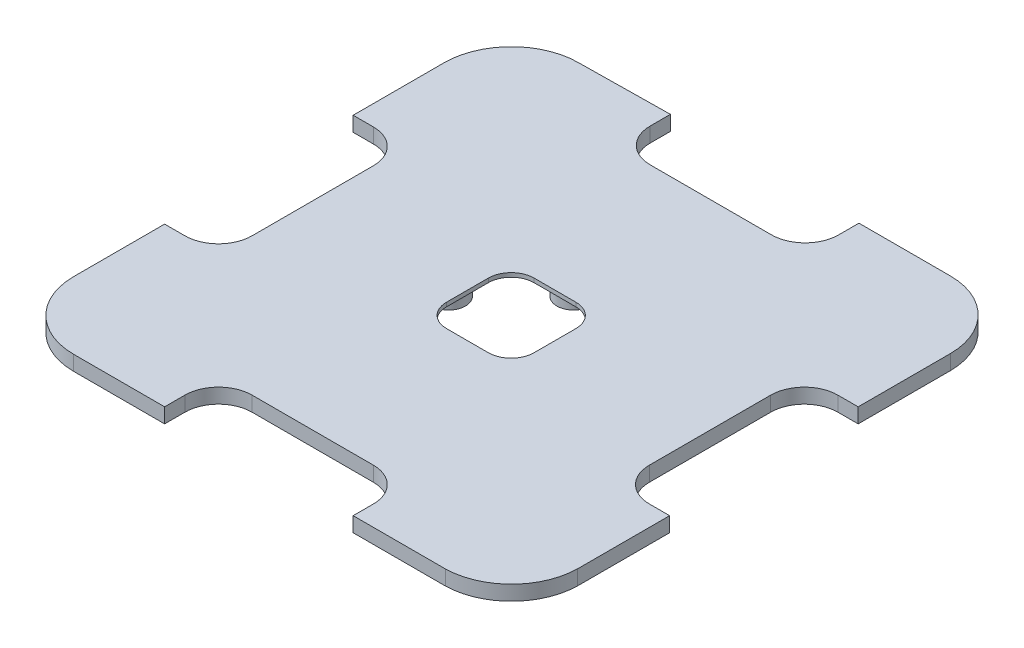
SolidWorks part; units mm, degrees
ref_plane "Front Plane" through (0, 0, 0) normal (0, 0, 1) x (1, 0, 0)
ref_plane "Top Plane" through (0, 0, 0) normal (0, 1, 0) x (1, 0, 0)
ref_plane "Right Plane" through (0, 0, 0) normal (1, 0, 0) x (0, 0, -1)
sketch "Sketch6" plane through (0, 0, 0) normal (0, 1, 0) x (1, 0, 0)
  line L0 (-27.9543, -74.9894) -> (-27.9543, -68.9894)
  line L4 (-54.9544, -74.9894) -> (-27.9543, -74.9894)
  line L8 (28.0457, -74.9894) -> (28.0457, -68.9894)
  line L9 (18.0457, -58.9894) -> (-17.9543, -58.9894)
  line L10 (28.0457, -74.9894) -> (55.5119, -74.9894)
  line L11 (27.922, 75.3686) -> (27.9223, 69.3686)
  line L12 (-18.0772, 59.3662) -> (17.9228, 59.3681)
  line L13 (-28.078, 75.3657) -> (-28.0777, 69.3657)
  line L14 (-28.078, 75.3657) -> (-54.9215, 75.0001)
  line L15 (27.922, 75.3686) -> (55.0446, 75.3701)
  line L16 (-74.9543, 28.0106) -> (-68.9543, 28.0106)
  line L17 (-58.9543, -17.9894) -> (-58.9543, 18.0106)
  line L18 (-74.9543, -27.9894) -> (-68.9543, -27.9894)
  line L22 (75.0457, -27.9894) -> (69.0457, -27.9894)
  line L23 (59.0457, 18.0106) -> (59.0457, -17.9894)
  line L24 (75.0457, 28.0106) -> (69.0457, 28.0106)
  line L25 (75.0457, 28.0106) -> (75.0457, 55.37)
  line L26 (75.0457, -27.9894) -> (75.0457, -55.3762)
  line L27 (-74.9543, 55.0001) -> (-74.9543, 28.0106)
  line L28 (-74.9543, -27.9894) -> (-74.9543, -54.9895)
  line L29 (-73.4543, 55.0001) -> (-73.4543, 29.5106)
  line L30 (-73.4543, 29.5106) -> (-68.9543, 29.5106)
  line L31 (-57.4543, -17.9894) -> (-57.4543, 18.0106)
  line L32 (-73.4543, -29.4894) -> (-68.9543, -29.4894)
  line L33 (-73.4543, -29.4894) -> (-73.4543, -54.9895)
  line L34 (-54.9544, -73.4894) -> (-36.0728, -73.4894)
  line L35 (-29.4543, -73.4894) -> (-29.4543, -68.9894)
  line L36 (18.0457, -57.4894) -> (-17.9543, -57.4894)
  line L37 (29.5457, -73.4894) -> (29.5457, -68.9894)
  line L38 (29.5457, -73.4894) -> (55.4924, -73.4894)
  line L39 (73.5457, -29.4894) -> (73.5457, -55.3598)
  line L40 (73.5457, -29.4894) -> (69.0457, -29.4894)
  line L41 (57.5457, 18.0106) -> (57.5457, -17.9894)
  line L42 (73.5457, 29.5106) -> (69.0457, 29.5106)
  line L43 (73.5457, 29.5106) -> (73.5457, 55.37)
  line L44 (29.4221, 73.8687) -> (55.0447, 73.8701)
  line L45 (29.4221, 73.8687) -> (29.4223, 69.3687)
  line L46 (-18.0771, 57.8662) -> (17.9229, 57.8681)
  line L47 (-29.5779, 73.8451) -> (-29.5777, 69.3656)
  line L48 (-29.5779, 73.8451) -> (-54.9127, 73.5)
  line L49 (-34.4232, -73.4894) -> (-32.1323, -73.4894)
  line L50 (-54.9544, -73.4894) -> (-29.4543, -73.4894) construction
  line L51 (-30.4828, -73.4894) -> (-29.4543, -73.4894)
  line L52 (-27.9543, 75.0106) -> (-27.9543, 69.0106) [skipped]
  line L53 (28.0457, 75.0106) -> (28.0457, 69.0106) [skipped]
  line L54 (-17.9543, 59.0106) -> (18.0457, 59.0106) [skipped]
  circle A0 centre (-63.8144, 56.4001) radius 4.1
  circle A1 centre (-56.2944, 63.8801) radius 4.1
  circle A2 centre (-45.5, 65.0002) radius 4.1
  circle A3 centre (-33.77, 60.5602) radius 4.1
  circle A5 centre (-47.06, 47.0602) radius 4.1
  circle A6 centre (-65, 45.5702) radius 4.1
  circle A7 centre (-22.73, 52.0902) radius 4.1
  circle A8 centre (-10.97, 52.0902) radius 4.1
  circle A9 centre (-13.21, 40.9602) radius 4.1
  circle A10 centre (-5.58, 29.2102) radius 4.1
  circle A11 centre (-39.63, 39.6302) radius 4.1
  circle A12 centre (-32.2, 32.2002) radius 4.1
  circle A13 centre (-24.77, 24.7702) radius 4.1
  circle A14 centre (-60.62, 33.8602) radius 4.1
  circle A15 centre (-52.09, 22.8302) radius 4.1
  circle A17 centre (-52.09, 10.9702) radius 4.1
  circle A18 centre (-41.09, 13.3102) radius 4.1
  circle A19 centre (-29.37, 5.6802) radius 4.1
  circle A21 centre (56.4456, 64.23) radius 4.1
  circle A22 centre (63.9256, 56.71) radius 4.1
  circle A23 centre (65, 45.5002) radius 4.1
  circle A24 centre (45.57, 65.0002) radius 4.1
  circle A25 centre (33.86, 60.6202) radius 4.1
  circle A26 centre (47.06, 47.0602) radius 4.1
  circle A27 centre (39.63, 39.6302) radius 4.1
  circle A28 centre (22.83, 52.0902) radius 4.1
  circle A30 centre (10.97, 52.0902) radius 4.1
  circle A31 centre (13.31, 41.0902) radius 4.1
  circle A32 centre (5.68, 29.3702) radius 4.1
  circle A33 centre (24.77, 24.7702) radius 4.1
  circle A34 centre (32.2, 32.2002) radius 4.1
  circle A35 centre (60.56, 33.7702) radius 4.1
  circle A36 centre (52.09, 22.7302) radius 4.1
  circle A38 centre (52.09, 10.9702) radius 4.1
  circle A39 centre (40.96, 13.2102) radius 4.1
  circle A40 centre (29.21, 5.5802) radius 4.1
  circle A42 centre (63.8611, -56.3467) radius 4.1
  circle A43 centre (56.3411, -63.8267) radius 4.1
  circle A44 centre (45.5, -64.9998) radius 4.1
  circle A45 centre (65, -45.5698) radius 4.1
  circle A46 centre (60.62, -33.8598) radius 4.1
  circle A47 centre (47.06, -47.0598) radius 4.1
  circle A48 centre (39.63, -39.6298) radius 4.1
  circle A49 centre (52.09, -22.8298) radius 4.1
  circle A51 centre (52.09, -10.9698) radius 4.1
  circle A52 centre (41.09, -13.3098) radius 4.1
  circle A53 centre (29.37, -5.6798) radius 4.1
  circle A54 centre (24.77, -24.7698) radius 4.1
  circle A55 centre (32.2, -32.1998) radius 4.1
  circle A56 centre (33.77, -60.5598) radius 4.1
  circle A57 centre (22.73, -52.0898) radius 4.1
  circle A59 centre (10.97, -52.0898) radius 4.1
  circle A60 centre (13.21, -40.9598) radius 4.1
  circle A61 centre (5.58, -29.2098) radius 4.1
  circle A63 centre (-56.3544, -63.8492) radius 4.1
  circle A64 centre (-63.8344, -56.3292) radius 4.1
  circle A65 centre (-65, -45.4998) radius 4.1
  circle A66 centre (-45.57, -64.9998) radius 4.1
  circle A67 centre (-33.86, -60.6198) radius 4.1
  circle A68 centre (-47.06, -47.0598) radius 4.1
  circle A69 centre (-39.63, -39.6298) radius 4.1
  circle A70 centre (-22.83, -52.0898) radius 4.1
  circle A72 centre (-10.97, -52.0898) radius 4.1
  circle A73 centre (-13.21, -41.1198) radius 4.1
  circle A74 centre (-5.68, -29.3698) radius 4.1
  circle A75 centre (-24.77, -24.7698) radius 4.1
  circle A76 centre (-32.2, -32.1998) radius 4.1
  circle A77 centre (-60.56, -33.7698) radius 4.1
  circle A78 centre (-52.09, -22.7298) radius 4.1
  circle A80 centre (-52.09, -10.9698) radius 4.1
  circle A81 centre (-40.96, -13.2098) radius 4.1
  circle A82 centre (-29.21, -5.5798) radius 4.1
  circle A85 centre (0, 52.0902) radius 4.1
  circle A86 centre (0, 41.1202) radius 4.1
  circle A87 centre (0, 18.5802) radius 4.1
  circle A89 centre (52.09, 0.0002) radius 4.1
  circle A90 centre (41.12, 0.0002) radius 4.1
  circle A91 centre (18.58, 0.0002) radius 4.1
  circle A93 centre (0, -51.9998) radius 4.1
  circle A94 centre (0, -41.1198) radius 4.1
  circle A95 centre (0, -18.5798) radius 4.1
  circle A97 centre (-52.09, 0.0002) radius 4.1
  circle A98 centre (-41.12, 0.0002) radius 4.1
  circle A99 centre (-18.58, 0.0002) radius 4.1
  arc A105 (-32.1323, -73.4894) -> (-34.4232, -73.4894) centre (-33.2778, -70.9893) ccw
  circle A106 centre (-54.9544, 55.0001) radius 1.85
  circle A107 centre (55.0456, 55.37) radius 1.85
  circle A108 centre (17, 17.0002) radius 1.85
  circle A109 centre (-17, 17.0002) radius 1.85
  circle A110 centre (-17, -16.9998) radius 1.85
  circle A111 centre (17, -16.9998) radius 1.85
  circle A112 centre (-54.9544, -54.9895) radius 1.85
  circle A113 centre (55.001, -54.9467) radius 1.85
  arc A114 (-55.8403, 58.9008) -> (-58.8318, 55.9826) centre (-54.9544, 55.0001) ccw
  circle A115 centre (-17, 17.0002) radius 4
  circle A116 centre (-17, -16.9998) radius 4
  arc A117 (-55.2138, -58.981) -> (-58.9428, -55.2938) centre (-54.9544, -54.9895) ccw
  circle A118 centre (17, -16.9998) radius 4
  arc A119 (55.8869, -58.8474) -> (58.8786, -55.9289) centre (55.001, -54.9467) ccw
  circle A120 centre (17, 17.0002) radius 4
  arc A121 (55.3065, 59.3615) -> (59.034, 55.6746) centre (55.0456, 55.37) ccw
  arc A122 (-74.9543, 55.0001) -> (-54.9215, 75.0001) centre (-54.9544, 55.0001) cw
  arc A123 (75.0457, 55.37) -> (55.0446, 75.3701) centre (55.0456, 55.37) ccw
  arc A124 (-74.9543, -54.9895) -> (-54.9544, -74.9894) centre (-54.9544, -54.9895) ccw
  arc A125 (55.5119, -74.9894) -> (75.0457, -55.3762) centre (55.001, -54.9467) ccw
  circle A126 centre (-45.5, 65.0002) radius 5
  arc A127 (-58.8318, 55.9826) -> (-58.9458, 55.261) centre (-63.8144, 56.4001) ccw
  arc A128 (-55.2589, 58.9885) -> (-55.8403, 58.9008) centre (-56.2944, 63.8801) ccw
  circle A129 centre (-33.77, 60.5602) radius 5
  circle A131 centre (-22.73, 52.0902) radius 5
  circle A132 centre (-10.97, 52.0902) radius 5
  circle A133 centre (0, 52.0902) radius 5
  circle A134 centre (10.97, 52.0902) radius 5
  circle A137 centre (33.86, 60.6202) radius 5
  circle A138 centre (45.57, 65.0002) radius 5
  arc A139 (56.0281, 59.2475) -> (55.3065, 59.3615) centre (56.4456, 64.23) ccw
  arc A140 (59.034, 55.6746) -> (58.9463, 56.2559) centre (63.9256, 56.71) ccw
  circle A141 centre (65, 45.5002) radius 5
  circle A142 centre (47.06, 47.0602) radius 5
  circle A143 centre (39.63, 39.6302) radius 5
  circle A144 centre (22.83, 52.0902) radius 5
  circle A145 centre (13.31, 41.0902) radius 5
  circle A146 centre (0, 41.1202) radius 5
  circle A147 centre (-13.21, 40.9602) radius 5
  circle A148 centre (-5.58, 29.2102) radius 5
  circle A149 centre (5.68, 29.3702) radius 5
  circle A150 centre (0, 18.5802) radius 5
  circle A151 centre (-47.06, 47.0602) radius 5
  circle A152 centre (-39.63, 39.6302) radius 5
  circle A153 centre (-32.2, 32.2002) radius 5
  circle A154 centre (-24.77, 24.7702) radius 5
  arc A155 (-58.9458, 55.261) -> (-55.2589, 58.9885) centre (-54.9544, 55.0001) ccw
  circle A157 centre (-65, 45.5702) radius 5
  circle A158 centre (-60.62, 33.8602) radius 5
  circle A160 centre (-52.09, 22.8302) radius 5
  circle A161 centre (-41.09, 13.3102) radius 5
  circle A162 centre (-52.09, 10.9702) radius 5
  circle A164 centre (-52.09, 0.0002) radius 5
  circle A165 centre (-41.12, 0.0002) radius 5
  circle A166 centre (-29.37, 5.6802) radius 5
  circle A167 centre (-18.58, 0.0002) radius 5
  circle A168 centre (-29.21, -5.5798) radius 5
  circle A169 centre (-40.96, -13.2098) radius 5
  circle A170 centre (-52.09, -10.9698) radius 5
  circle A172 centre (-52.09, -22.7298) radius 5
  circle A173 centre (-60.56, -33.7698) radius 5
  circle A174 centre (-65, -45.4998) radius 5
  arc A175 (-58.9428, -55.2938) -> (-58.855, -55.8754) centre (-63.8344, -56.3292) ccw
  arc A176 (-55.9383, -58.8665) -> (-55.2138, -58.981) centre (-56.3544, -63.8492) ccw
  arc A177 (-58.855, -55.8754) -> (-55.9383, -58.8665) centre (-54.9544, -54.9895) ccw
  circle A178 centre (-45.57, -64.9998) radius 5
  circle A179 centre (-47.06, -47.0598) radius 5
  circle A180 centre (-33.86, -60.6198) radius 5
  arc A181 (-30.4828, -73.4894) -> (-36.0728, -73.4894) centre (-33.2778, -70.9893) ccw
  circle A185 centre (-22.83, -52.0898) radius 5
  circle A186 centre (-39.63, -39.6298) radius 5
  circle A187 centre (-32.2, -32.1998) radius 5
  circle A188 centre (-24.77, -24.7698) radius 5
  circle A189 centre (0, -18.5798) radius 5
  circle A190 centre (-5.68, -29.3698) radius 5
  circle A191 centre (5.58, -29.2098) radius 5
  circle A192 centre (-13.21, -41.1198) radius 5
  circle A193 centre (-10.97, -52.0898) radius 5
  circle A194 centre (0, -51.9998) radius 5
  circle A195 centre (10.97, -52.0898) radius 5
  circle A196 centre (0, -41.1198) radius 5
  circle A197 centre (13.21, -40.9598) radius 5
  circle A198 centre (22.73, -52.0898) radius 5
  circle A199 centre (33.77, -60.5598) radius 5
  circle A200 centre (45.5, -64.9998) radius 5
  arc A201 (55.3057, -58.9351) -> (55.8869, -58.8474) centre (56.3411, -63.8267) ccw
  arc A202 (58.8786, -55.9289) -> (58.9925, -55.2079) centre (63.8611, -56.3467) ccw
  arc A203 (58.9925, -55.2079) -> (55.3057, -58.9351) centre (55.001, -54.9467) ccw
  circle A204 centre (47.06, -47.0598) radius 5
  circle A205 centre (39.63, -39.6298) radius 5
  circle A206 centre (32.2, -32.1998) radius 5
  circle A207 centre (24.77, -24.7698) radius 5
  circle A208 centre (65, -45.5698) radius 5
  circle A209 centre (60.62, -33.8598) radius 5
  circle A210 centre (52.09, -22.8298) radius 5
  circle A212 centre (41.09, -13.3098) radius 5
  circle A213 centre (52.09, -10.9698) radius 5
  circle A215 centre (52.09, 0.0002) radius 5
  circle A216 centre (41.12, 0.0002) radius 5
  circle A217 centre (29.37, -5.6798) radius 5
  circle A218 centre (18.58, 0.0002) radius 5
  circle A219 centre (29.21, 5.5802) radius 5
  circle A220 centre (40.96, 13.2102) radius 5
  circle A221 centre (52.09, 10.9702) radius 5
  circle A223 centre (52.09, 22.7302) radius 5
  circle A224 centre (60.56, 33.7702) radius 5
  circle A225 centre (32.2, 32.2002) radius 5
  circle A226 centre (24.77, 24.7702) radius 5
  arc A227 (58.9463, 56.2559) -> (56.0281, 59.2475) centre (55.0456, 55.37) ccw
  arc A228 (28.0457, -68.9894) -> (18.0457, -58.9894) centre (18.0457, -68.9894) ccw
  arc A229 (-17.9543, -58.9894) -> (-27.9543, -68.9894) centre (-17.9543, -68.9894) ccw
  arc A230 (17.9228, 59.3681) -> (27.9223, 69.3686) centre (17.9223, 69.3681) ccw
  arc A231 (-28.0777, 69.3657) -> (-18.0772, 59.3662) centre (-18.0777, 69.3662) ccw
  arc A232 (-58.9543, 18.0106) -> (-68.9543, 28.0106) centre (-68.9543, 18.0106) ccw
  arc A233 (-68.9543, -27.9894) -> (-58.9543, -17.9894) centre (-68.9543, -17.9894) ccw
  arc A236 (59.0457, -17.9894) -> (69.0457, -27.9894) centre (69.0457, -17.9894) ccw
  arc A237 (69.0457, 28.0106) -> (59.0457, 18.0106) centre (69.0457, 18.0106) ccw
  arc A238 (-57.4543, 18.0106) -> (-68.9543, 29.5106) centre (-68.9543, 18.0106) ccw
  arc A239 (-68.9543, -29.4894) -> (-57.4543, -17.9894) centre (-68.9543, -17.9894) ccw
  arc A240 (-73.4543, -54.9895) -> (-54.9544, -73.4894) centre (-54.9544, -54.9895) ccw
  arc A241 (-17.9543, -57.4894) -> (-29.4543, -68.9894) centre (-17.9543, -68.9894) ccw
  arc A242 (29.5457, -68.9894) -> (18.0457, -57.4894) centre (18.0457, -68.9894) ccw
  arc A243 (55.4924, -73.4894) -> (73.5457, -55.3598) centre (55.001, -54.9467) ccw
  arc A244 (57.5457, -17.9894) -> (69.0457, -29.4894) centre (69.0457, -17.9894) ccw
  arc A245 (69.0457, 29.5106) -> (57.5457, 18.0106) centre (69.0457, 18.0106) ccw
  arc A246 (73.5457, 55.37) -> (55.0447, 73.8701) centre (55.0456, 55.37) ccw
  arc A247 (17.9229, 57.8681) -> (29.4223, 69.3687) centre (17.9223, 69.3681) ccw
  arc A248 (-29.5777, 69.3656) -> (-18.0771, 57.8662) centre (-18.0777, 69.3662) ccw
  arc A249 (-73.4543, 55.0001) -> (-54.9127, 73.5) centre (-54.9544, 55.0001) cw
  arc A250 (-27.9543, 69.0106) -> (-17.9543, 59.0106) centre (-17.9543, 69.0106) ccw [skipped]
  arc A251 (18.0457, 59.0106) -> (28.0457, 69.0106) centre (18.0457, 69.0106) ccw [skipped]
  point P8 (0.0457, -74.9894)
  point P66 (0, 0)
  point P181 (-0.0142, 0.1889)
  point P250 (0.0457, 0.0106)
  dimension "D1" = 8.2
  dimension "D3" = 5.5
  dimension "D4" = 3.7
  dimension "D5" = 8
  dimension "D6" = 10
  dimension "D7" = 7.5
  dimension "D8" = 10
  dimension "D9" = 10
  dimension "D10" = 10
  dimension "D11" = 10
  dimension "D12" = 10
  dimension "D13" = 10
  dimension "D14" = 10
  dimension "D15" = 10
  dimension "D16" = 10
  dimension "D17" = 10
  dimension "D18" = 10
  dimension "D19" = 28
  dimension "D20" = 6
  dimension "D21" = 10
  dimension "D22" = 10
  dimension "D23" = 10
  dimension "D24" = 10
  dimension "D25" = 10
  dimension "D26" = 10
  dimension "D27" = 10
  dimension "D28" = 10
  dimension "D29" = 10
  dimension "D30" = 10
  dimension "D31" = 10
  dimension "D32" = 10
  dimension "D33" = 10
  dimension "D34" = 10
  dimension "D35" = 10
  dimension "D36" = 20
  dimension "D38" = 20
  dimension "D37" = 20
  dimension "D39" = 6
  dimension "D40" = 28
  dimension "D41" = 36
  dimension "D45" = 47
  dimension "D46" = 47
  dimension "D44" = 1.5
  dimension "D42" = 2
  dimension "D43" = 4
extrude "Boss-Extrude3" add sketch "Sketch6" along normal blind 3.2 contours A237 L24 L25 A123 L15 L11 A230 L12 A231 L13 L14 A122 L27 L16 A232 L17 A233 L18 L28 A124 L4 L0 A229 L9 A228 L8 L10 A125 L26 L22 A236 L23 L50 L34 A240 L33 L32 A239 L31 A238 L30 L29 A249 L48 L47 A248 L46 A247 L45 L44 | A127 A155 A128 A114 A0 A1 A106 | A126 A2 | A129 A3 | A151 A5 | A152 A11 | A158 A14 | A160 A15 | A162 A17 | A161 A18 | A164 A97 | A165 A98 | A170 A80 | A166 A19 | A154 A13 | A153 A12 | A115 A109 | A167 A99 | A168 A82 | A169 A81 | A116 A110 | A172 A78 | A188 A75 | A187 A76 | A186 A69 | A175 A177 A176 A117 A63 A64 A112 | A174 A65 | A173 A77 | A179 A68 | A178 A66 | A180 A67 | A185 A70 | A189 A95 | A118 A111 | A207 A54 | A191 A61 | A190 A74 | A196 A94 | A197 A60 | A194 A93 | A195 A59 | A192 A73 | A193 A72 | A198 A57 | A199 A56 | A200 A44 | A202 A203 A201 A119 A42 A43 A113 | A204 A47 | A205 A48 | A206 A55 | A208 A45 | A209 A46 | A210 A49 | A213 A51 | A212 A52 | A217 A53 | A216 A90 | A215 A89 | A120 A108 | A218 A91 | A219 A40 | A220 A39 | A221 A38 | A223 A36 | A150 A87 | A226 A33 | A149 A32 | A145 A31 | A225 A34 | A131 A7 | A147 A9 | A148 A10 | A146 A86 | A132 A8 | A133 A85 | A134 A30 | A144 A28 | A140 A227 A139 A121 A21 A22 A107 | A137 A25 | A138 A24 | A142 A26 | A143 A27 | A141 A23 | A224 A35 | A157 A6 region at (-41.4543, 0, 74.777) region at (-57.0027, 0, -68.5743) region at (-20.8869, 0, -17.0002) region at (-20.8869, 0, 16.9998) region at (-57.0953, 0, 68.5383) region at (13.1131, 0, 16.9998) region at (57.0495, 0, 68.5208) region at (13.1131, 0, -17.0002) region at (57.1866, 0, -68.9191) region at (-50.3586, 0, -65.0002) region at (-38.6286, 0, -60.5602) region at (-27.5886, 0, -52.0902) region at (-15.8286, 0, -52.0902) region at (-4.8586, 0, -52.0902) region at (6.1114, 0, -52.0902) region at (29.0014, 0, -60.6202) region at (40.7114, 0, -65.0002) region at (60.1414, 0, -45.5002) region at (42.2014, 0, -47.0602) region at (34.7714, 0, -39.6302) region at (17.9714, 0, -52.0902) region at (8.4514, 0, -41.0902) region at (-4.8586, 0, -41.1202) region at (-18.0686, 0, -40.9602) region at (-10.4386, 0, -29.2102) region at (0.8214, 0, -29.3702) region at (-4.8586, 0, -18.5802) region at (-51.9186, 0, -47.0602) region at (-44.4886, 0, -39.6302) region at (-37.0586, 0, -32.2002) region at (-29.6286, 0, -24.7702) region at (-69.8586, 0, -45.5702) region at (-65.4786, 0, -33.8602) region at (-56.9486, 0, -22.8302) region at (-45.9486, 0, -13.3102) region at (-56.9486, 0, -10.9702) region at (-56.9486, 0, -0.0002) region at (-45.9786, 0, -0.0002) region at (-34.2286, 0, -5.6802) region at (-23.4386, 0, -0.0002) region at (-34.0686, 0, 5.5798) region at (-45.8186, 0, 13.2098) region at (-56.9486, 0, 10.9698) region at (-56.9486, 0, 22.7298) region at (-65.4186, 0, 33.7698) region at (-69.8586, 0, 45.4998) region at (-50.4286, 0, 64.9998) region at (-51.9186, 0, 47.0598) region at (-38.7186, 0, 60.6198) region at (-27.6886, 0, 52.0898) region at (-44.4886, 0, 39.6298) region at (-37.0586, 0, 32.1998) region at (-29.6286, 0, 24.7698) region at (-4.8586, 0, 18.5798) region at (-10.5386, 0, 29.3698) region at (0.7214, 0, 29.2098) region at (-18.0686, 0, 41.1198) region at (-15.8286, 0, 52.0898) region at (-4.8586, 0, 51.9998) region at (6.1114, 0, 52.0898)
sketch "Sketch7" plane through (0, 3.2, 0) normal (0, 1, 0) x (1, 0, 0)
  line L21 (-6.2, -13) -> (6.2, -13)
  line L22 (-13, -6.2) -> (-13, 6.2)
  line L23 (-6.2, 13) -> (6.2, 13)
  line L24 (13, -6.2) -> (13, 6.2)
  line L25 (-13, -13) -> (13, 13) construction
  line L26 (-13, 13) -> (13, -13) construction
  line L40 (69.0457, 28.0106) -> (75.0457, 28.0106)
  line L41 (75.0457, 28.0106) -> (75.0457, 55.37)
  line L42 (55.0446, 75.3701) -> (27.922, 75.3686)
  line L43 (27.922, 75.3686) -> (27.9223, 69.3686)
  line L44 (17.9228, 59.3681) -> (-18.0772, 59.3662)
  line L45 (-28.0777, 69.3657) -> (-28.078, 75.3657)
  line L46 (-28.078, 75.3657) -> (-54.9215, 75.0001)
  line L47 (-74.9543, 55.0001) -> (-74.9543, 28.0106)
  line L48 (-74.9543, 28.0106) -> (-68.9543, 28.0106)
  line L49 (-58.9543, 18.0106) -> (-58.9543, -17.9894)
  line L50 (-68.9543, -27.9894) -> (-74.9543, -27.9894)
  line L51 (-74.9543, -27.9894) -> (-74.9543, -54.9895)
  line L52 (-54.9544, -74.9894) -> (-27.9543, -74.9894)
  line L53 (-27.9543, -74.9894) -> (-27.9543, -68.9894)
  line L54 (-17.9543, -58.9894) -> (18.0457, -58.9894)
  line L55 (28.0457, -68.9894) -> (28.0457, -74.9894)
  line L56 (28.0457, -74.9894) -> (55.5119, -74.9894)
  line L57 (75.0457, -55.3762) -> (75.0457, -27.9894)
  line L58 (75.0457, -27.9894) -> (69.0457, -27.9894)
  line L59 (59.0457, -17.9894) -> (59.0457, 18.0106)
  line L60 (69.0457, 28.0106) -> (75.0457, 28.0106)
  line L61 (75.0457, 28.0106) -> (75.0457, 55.37)
  line L62 (55.0446, 75.3701) -> (27.922, 75.3686)
  line L63 (27.922, 75.3686) -> (27.9223, 69.3686)
  line L64 (17.9228, 59.3681) -> (-18.0772, 59.3662)
  line L65 (-28.0777, 69.3657) -> (-28.078, 75.3657)
  line L66 (-28.078, 75.3657) -> (-54.9215, 75.0001)
  line L67 (-74.9543, 55.0001) -> (-74.9543, 28.0106)
  line L68 (-74.9543, 28.0106) -> (-68.9543, 28.0106)
  line L69 (-58.9543, 18.0106) -> (-58.9543, -17.9894)
  line L70 (-68.9543, -27.9894) -> (-74.9543, -27.9894)
  line L71 (-74.9543, -27.9894) -> (-74.9543, -54.9895)
  line L72 (-54.9544, -74.9894) -> (-27.9543, -74.9894)
  line L73 (-27.9543, -74.9894) -> (-27.9543, -68.9894)
  line L74 (-17.9543, -58.9894) -> (18.0457, -58.9894)
  line L75 (28.0457, -68.9894) -> (28.0457, -74.9894)
  line L76 (28.0457, -74.9894) -> (55.5119, -74.9894)
  line L77 (75.0457, -55.3762) -> (75.0457, -27.9894)
  line L78 (75.0457, -27.9894) -> (69.0457, -27.9894)
  line L79 (59.0457, -17.9894) -> (59.0457, 18.0106)
  arc A12 (6.2, 13) -> (13, 6.2) centre (6.2, 6.2) cw
  arc A13 (6.2, -13) -> (13, -6.2) centre (6.2, -6.2) ccw
  arc A14 (-6.2, -13) -> (-13, -6.2) centre (-6.2, -6.2) cw
  arc A15 (-13, 6.2) -> (-6.2, 13) centre (-6.2, 6.2) cw
  arc A24 (69.0457, 28.0106) -> (59.0457, 18.0106) centre (69.0457, 18.0106) ccw
  arc A25 (75.0457, 55.37) -> (55.0446, 75.3701) centre (55.0456, 55.37) ccw
  arc A26 (17.9228, 59.3681) -> (27.9223, 69.3686) centre (17.9223, 69.3681) ccw
  arc A27 (-28.0777, 69.3657) -> (-18.0772, 59.3662) centre (-18.0777, 69.3662) ccw
  arc A28 (-54.9215, 75.0001) -> (-74.9543, 55.0001) centre (-54.9544, 55.0001) ccw
  arc A29 (-58.9543, 18.0106) -> (-68.9543, 28.0106) centre (-68.9543, 18.0106) ccw
  arc A30 (-68.9543, -27.9894) -> (-58.9543, -17.9894) centre (-68.9543, -17.9894) ccw
  arc A31 (-74.9543, -54.9895) -> (-54.9544, -74.9894) centre (-54.9544, -54.9895) ccw
  arc A32 (-17.9543, -58.9894) -> (-27.9543, -68.9894) centre (-17.9543, -68.9894) ccw
  arc A33 (28.0457, -68.9894) -> (18.0457, -58.9894) centre (18.0457, -68.9894) ccw
  arc A34 (55.5119, -74.9894) -> (75.0457, -55.3762) centre (55.001, -54.9467) ccw
  arc A35 (59.0457, -17.9894) -> (69.0457, -27.9894) centre (69.0457, -17.9894) ccw
  arc A36 (69.0457, 28.0106) -> (59.0457, 18.0106) centre (69.0457, 18.0106) ccw
  arc A37 (75.0457, 55.37) -> (55.0446, 75.3701) centre (55.0456, 55.37) ccw
  arc A38 (17.9228, 59.3681) -> (27.9223, 69.3686) centre (17.9223, 69.3681) ccw
  arc A39 (-28.0777, 69.3657) -> (-18.0772, 59.3662) centre (-18.0777, 69.3662) ccw
  arc A40 (-54.9215, 75.0001) -> (-74.9543, 55.0001) centre (-54.9544, 55.0001) ccw
  arc A41 (-58.9543, 18.0106) -> (-68.9543, 28.0106) centre (-68.9543, 18.0106) ccw
  arc A42 (-68.9543, -27.9894) -> (-58.9543, -17.9894) centre (-68.9543, -17.9894) ccw
  arc A43 (-74.9543, -54.9895) -> (-54.9544, -74.9894) centre (-54.9544, -54.9895) ccw
  arc A44 (-17.9543, -58.9894) -> (-27.9543, -68.9894) centre (-17.9543, -68.9894) ccw
  arc A45 (28.0457, -68.9894) -> (18.0457, -58.9894) centre (18.0457, -68.9894) ccw
  arc A46 (55.5119, -74.9894) -> (75.0457, -55.3762) centre (55.001, -54.9467) ccw
  arc A47 (59.0457, -17.9894) -> (69.0457, -27.9894) centre (69.0457, -17.9894) ccw
  point P0 (0, 0)
  dimension "D4" = 6.8
  dimension "D2" = 26
  dimension "D3" = 26
  dimension "D1" = 0
extrude "Boss-Extrude4" add sketch "Sketch7" along normal blind 1.2
